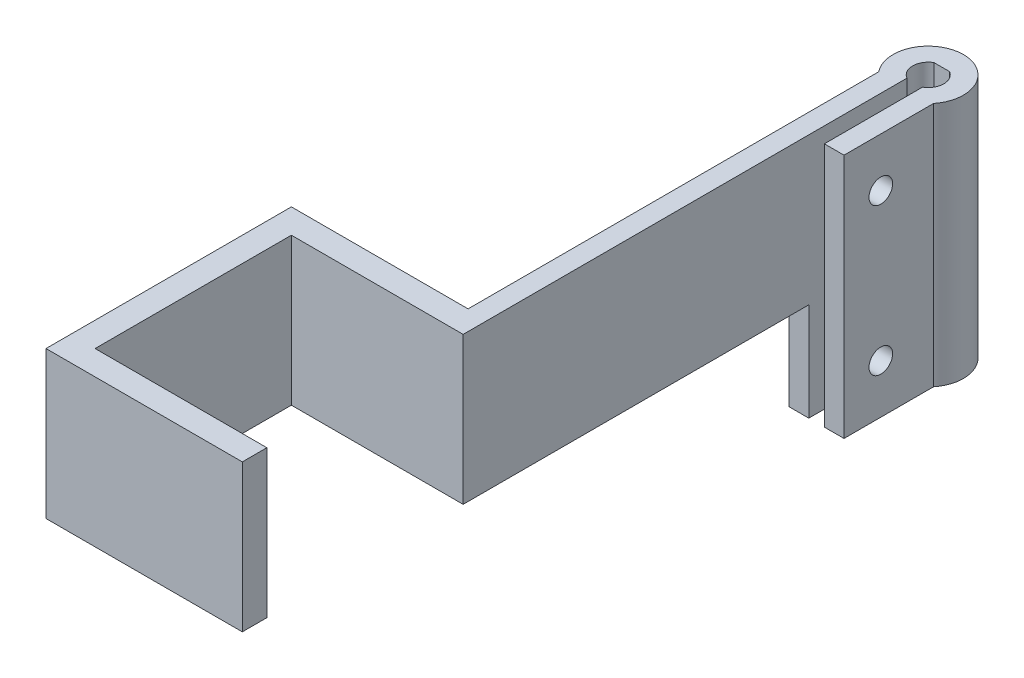
SolidWorks part; units mm, degrees
ref_plane "Front Plane" through (0, 0, 0) normal (0, 0, 1) x (1, 0, 0)
ref_plane "Top Plane" through (0, 0, 0) normal (0, 1, 0) x (1, 0, 0)
ref_plane "Right Plane" through (0, 0, 0) normal (1, 0, 0) x (0, 0, -1)
sketch "Sketch1" plane through (0, 0, 0) normal (0, 1, 0) x (1, 0, 0)
  line L0 (-1.5875, -2.7496) -> (-1.5875, -22.7496)
  line L1 (1.5875, -2.7496) -> (1.5875, -22.7496)
  line L2 (1.5875, 2.7496) -> (-1.5875, 2.7496)
  line L3 (5.5875, -4.5012) -> (5.5875, -22.7496)
  line L4 (-5.5875, -4.5012) -> (-5.5875, -22.7496)
  line L5 (-5.5875, -22.7496) -> (-1.5875, -22.7496)
  line L6 (1.5875, -22.7496) -> (5.5875, -22.7496)
  arc A0 (1.5875, -2.7496) -> (1.5875, 2.7496) centre (0, 0) ccw
  arc A1 (5.5875, -4.5012) -> (-5.5875, -4.5012) centre (0, 0) ccw
  arc A2 (-1.5875, 2.7496) -> (-1.5875, -2.7496) centre (0, 0) ccw
  arc A4 (1.5875, -2.7496) -> (-1.5875, -2.7496) centre (0, 0) ccw construction
  dimension "D1" = 3.175
  dimension "D2" = 20
  dimension "D3" = 3.175
  dimension "D5" = 3.175
  dimension "D4" = 4
extrude "Boss-Extrude1" add sketch "Sketch1" along normal blind 50
sketch "Sketch5" plane through (0, 50, 0) normal (0, 1, 0) x (1, 0, 0)
  line L2 (-41.5875, -88.175) -> (-41.5875, -138.175)
  line L3 (-41.5875, -138.175) -> (-1.5875, -138.175)
  line L4 (-1.5875, -138.175) -> (-1.5875, -133.175)
  line L5 (-1.5875, -133.175) -> (-36.5875, -133.175)
  line L9 (-1.5875, -22.7496) -> (-1.5875, -2.7496) construction
  line L10 (-36.5875, -93.175) -> (-1.5875, -93.175)
  line L12 (-36.5875, -133.175) -> (-36.5875, -93.175)
  line L13 (-41.5875, -88.175) -> (-5.5875, -88.175)
  line L14 (-5.5875, -88.175) -> (-5.5875, -22.7496)
  line L16 (-1.5875, -22.7496) -> (-1.5875, -93.175)
  line L17 (-1.5875, -22.7496) -> (-5.5875, -22.7496)
  line L18 (-18.6703, -3.175) -> (17.7565, -3.175) construction
  circle A0 centre (0, 0) radius 3.175 construction
  arc A1 (-1.5875, 2.7496) -> (-1.5875, -2.7496) centre (0, 0) ccw construction
  point P2 (-36.5875, -113.175)
  dimension "D2" = 110
  dimension "D1" = 35
  dimension "D3" = 40
  dimension "D4" = 5
  dimension "D5" = 5
  dimension "D7" = 5
extrude "Boss-Extrude2" add sketch "Sketch5" against normal blind 30
hole_wizard "M4 Clearance Hole1" positions "Sketch2" profile "Sketch3" hole size "M4" standard "ANSI Metric" end condition through all
sketch "Sketch2" plane through (5.5875, 0, 0) normal (1, 0, 0) x (0, 0, -1)
  line L2 (-22.7496, 50) -> (-22.7496, 0) construction
  line L3 (-22.7496, 0) -> (-4.5012, 0) construction
  line L4 (-22.7496, 50) -> (-4.5012, 50) construction
  point P0 (-15.2496, 40)
  point P4 (-15.2496, 10)
  dimension "D1" = 10
  dimension "D2" = 10
  dimension "D3" = 7.5
sketch "Sketch3" plane through (5.5875, 40, 15.2496) normal (0, 1, 0) x (0, 0, -1)
  line L0 (0, 0) -> (0, 47.175)
  line L1 (0, 47.175) -> (2.4, 47.175)
  line L2 (2.4, 47.175) -> (2.4, 0)
  line L5 (2.4, 0) -> (0, 0)
  line L11 (0, -6.35) -> (0, 107.95) construction
  dimension "Thru Hole Dia." = 4.8
  dimension "Thru Hole Depth" = 47.175
